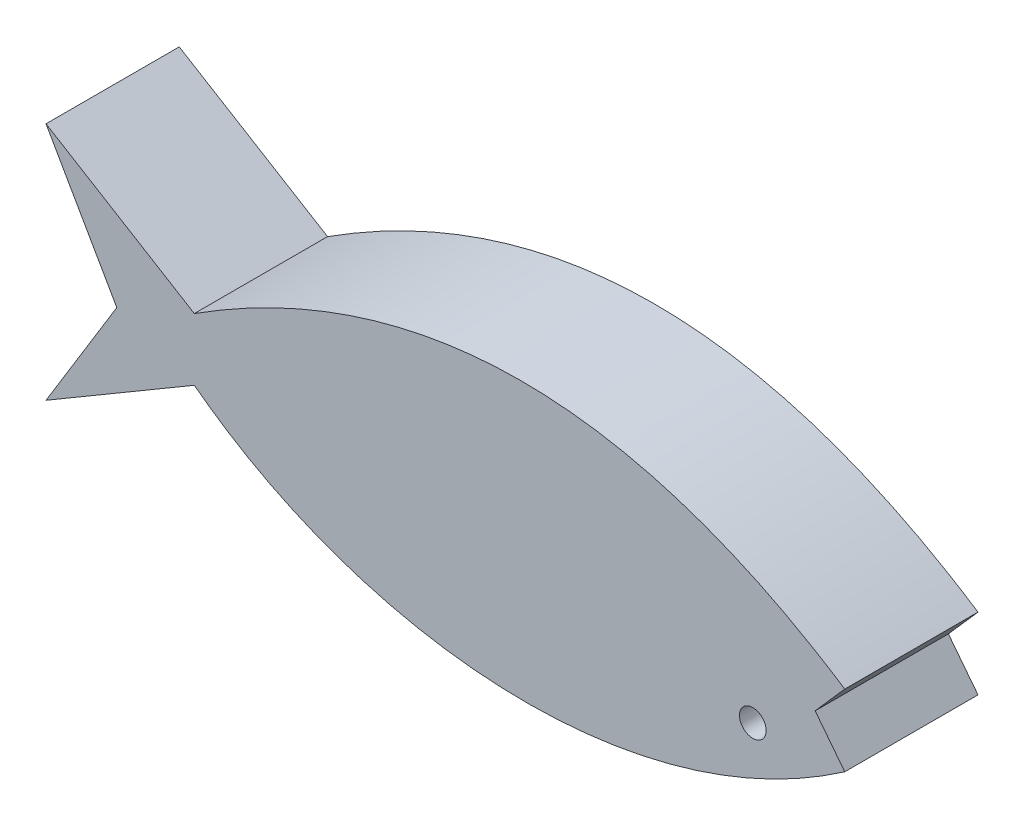
SolidWorks part; units mm, degrees
ref_plane "Front" through (0, 0, 0) normal (0, 0, 1) x (1, 0, 0)
ref_plane "Top" through (0, 0, 0) normal (0, 1, 0) x (1, 0, 0)
ref_plane "Right" through (0, 0, 0) normal (1, 0, 0) x (0, 0, -1)
sketch "Sketch2" plane through (0, 0, 0) normal (0, 0, -1) x (1, 0, 0)
  line L0 (29.973, 6.6427) -> (28.8624, 5.2157)
  line L1 (28.8624, 5.2157) -> (29.973, 3.9538)
  line L2 (5.5653, 6.2857) -> (0, 9.5561)
  line L3 (0, 9.5561) -> (2.6565, 5.2157)
  line L4 (2.6565, 5.2157) -> (0, 0.5701)
  line L5 (0, 0.5701) -> (5.5653, 3.9538)
  circle A0 centre (26.5226, 6.7807) radius 0.5001
  spline S0 degree 3 poles (5.5653, 6.2857) (12.0373, 11.2173) (22.1418, 12.0787) (29.973, 6.6427) knots 0 0 0 0 1 1 1 1
  spline S1 degree 2 poles (5.5653, 3.9538) (17.9191, -3.9397) (29.973, 3.9538) knots 0 0 0 1 1 1
extrude "Boss-Extrude1" add sketch "Sketch2" along normal blind 5
ref_plane "Fish Top Plane" through (0, 0, -5) normal (0, 0, -1) x (1, 0, 0)
sketch "Sketch4" plane through (0, 0, -5) normal (0, 0, -1) x (1, 0, 0)
  line L0 (18.0431, 7.7171) -> (20.1106, 7.7171)
  line L1 (22.551, 4.521) -> (22.551, 2.4779)
  line L2 (22.551, 2.4779) -> (13.2056, 2.4779)
  line L3 (13.2056, 2.4779) -> (13.2056, 5.037)
  line L4 (13.2056, 5.037) -> (19.2114, 5.037)
  spline S0 degree 3 poles (19.2114, 5.037) (18.7533, 5.9364) (18.1557, 6.7159) (18.0431, 7.7171) knots 0 0 0 0 1 1 1 1
  spline S1 degree 2 poles (20.1106, 7.7171) (20.5703, 5.7597) (22.551, 4.521) knots 0 0 0 1 1 1
extrude "Boss-Extrude2" add sketch "Sketch4" along normal blind 1
